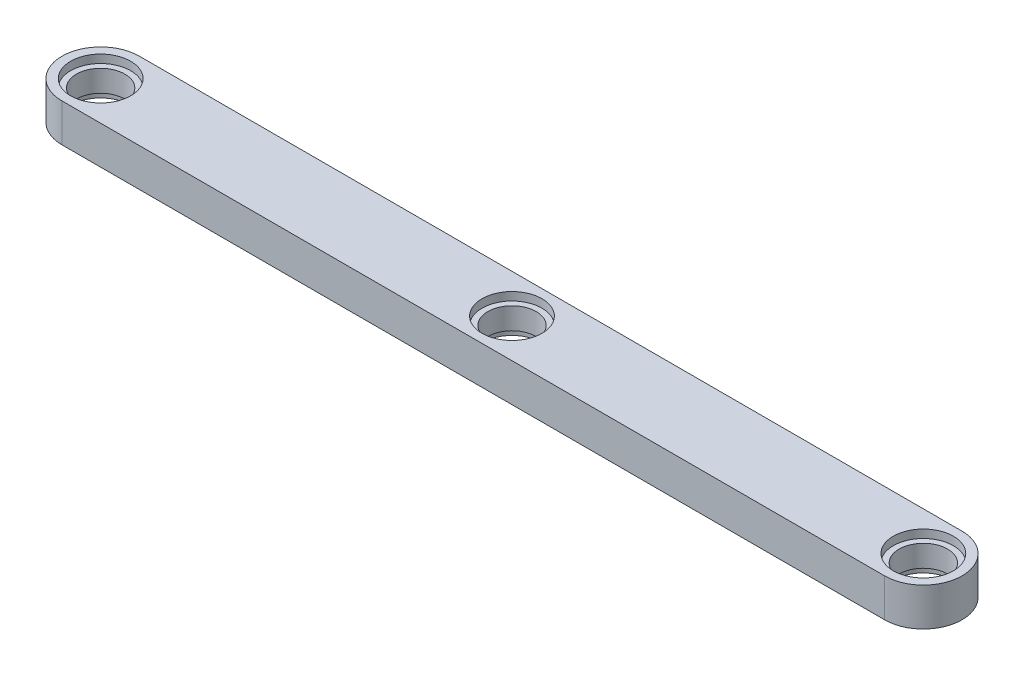
SolidWorks part; units mm, degrees
ref_plane "Front Plane" through (0, 0, 0) normal (0, 0, 1) x (1, 0, 0)
ref_plane "Top Plane" through (0, 0, 0) normal (0, 1, 0) x (1, 0, 0)
ref_plane "Right Plane" through (0, 0, 0) normal (1, 0, 0) x (0, 0, -1)
sketch "Croquis1" plane through (0, 0, 0) normal (0, 1, 0) x (1, 0, 0)
  line L0 (0, 0) -> (85, 0) construction
  line L1 (0, 4) -> (85, 4)
  line L2 (0, -4) -> (85, -4)
  circle A0 centre (0, 0) radius 3.1
  circle A1 centre (0, 0) radius 2.5
  circle A2 centre (85, 0) radius 3.1
  circle A3 centre (85, 0) radius 2.5
  arc A4 (0, 4) -> (0, -4) centre (0, 0) ccw
  arc A5 (85, -4) -> (85, 4) centre (85, 0) ccw
  circle A6 centre (42.5, 0) radius 2.5
  circle A7 centre (42.5, 0) radius 3.1
  point P7 (42.5, 0)
  dimension "D1" = 5
  dimension "D2" = 6.2
  dimension "D3" = 4
  dimension "D4" = 85
extrude "Saliente-Extruir1" add sketch "Croquis1" along normal blind 3.935 contours L2 A5 L1 A4 A0 A2 region at (42.5, 0, -3.9067)
extrude "Saliente-Extruir2" add sketch "Croquis1<3>" along normal offset from surface (2.235 mm away) 0.85 from offset 0.85 contours A1 A0 | A2 A3 | L0 A7 A6 | A7 L0 A6 region at (-3.0123, 0, 0) region at (85, 0, -3.0123) region at (42.5, 0, -3.0307) region at (39.7, 0, 0.0693) up to face at (42.5, 3.935, 3.1)
sketch "Croquis1<3>" plane through (0, 0, 0) normal (0, 1, 0) x (1, 0, 0) same geometry as "Croquis1"
equation "\"longitud\"=85"
equation "\"D4@Croquis1\"=\"longitud\""
equation "\"ancho\"= 7.87"
equation "\"offset\"=0.85"
equation "\"D19@Saliente-Extruir2\"=\"offset\""
equation "\"D1@Saliente-Extruir2\"=\"offset\""
equation "\"D1@Saliente-Extruir1\"=\"ancho\"/2"
